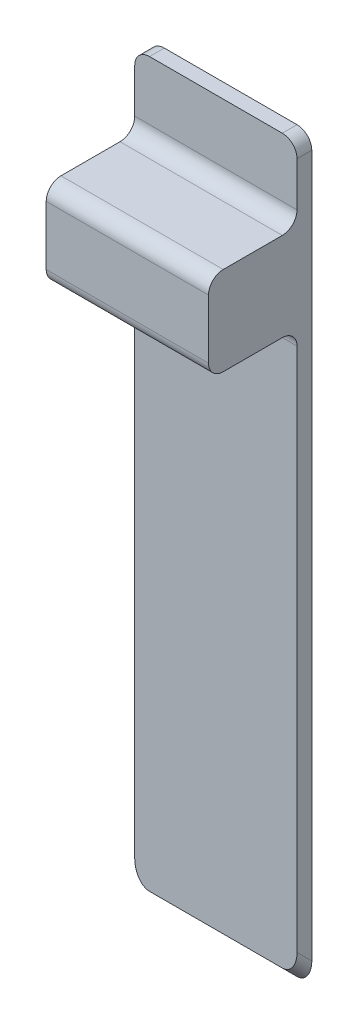
SolidWorks part; units mm, degrees
ref_plane "Front Plane" through (0, 0, 0) normal (0, 0, 1) x (1, 0, 0)
ref_plane "Top Plane" through (0, 0, 0) normal (0, 1, 0) x (1, 0, 0)
ref_plane "Right Plane" through (0, 0, 0) normal (1, 0, 0) x (0, 0, -1)
sketch "Szkic1" plane through (0, 0, 0) normal (0, 0, 1) x (1, 0, 0)
  line L0 (5.5, 25) -> (-5.5, -25) construction
  line L1 (-5.5, 25) -> (5.5, 25)
  line L2 (-5.5, 25) -> (-5.5, -25)
  line L3 (-5.5, -25) -> (5.5, -25)
  line L4 (5.5, 25) -> (5.5, -25)
  dimension "D1" = 11
  dimension "D2" = 50
extrude "Dodanie-wyciągnięcie1" add sketch "Szkic1" along normal blind 1
chamfer "Sfazowanie1" distance 1 angle 45 1 edges at (0, -25, 1)
sketch "Szkic2" plane through (0, 0, 1) normal (0, 0, 1) x (1, 0, 0)
  line L0 (-5.5, 25) -> (-5.5, -24) construction
  line L1 (-5.5, 20) -> (5.5, 20)
  line L2 (-5.5, 20) -> (-5.5, 14)
  line L3 (-5.5, 14) -> (5.5, 14)
  line L4 (5.5, 20) -> (5.5, 14)
  line L5 (5.5, -24) -> (5.5, 25) construction
  line L6 (5.5, 25) -> (-5.5, 25) construction
  dimension "D1" = 6
  dimension "D2" = 5
extrude "Dodanie-wyciągnięcie2" add sketch "Szkic2" along normal blind 6
fillet "Zaokrąglenie1" radius 1 8 edges at (0, 14, 7) (0, 20, 7) (0, 20, 1) (0, 14, 1) (-5.5, 25, 0.5) (-5.5, -24.5, 0.5) (5.5, -24.5, 0.5) (5.5, 25, 0.5)
